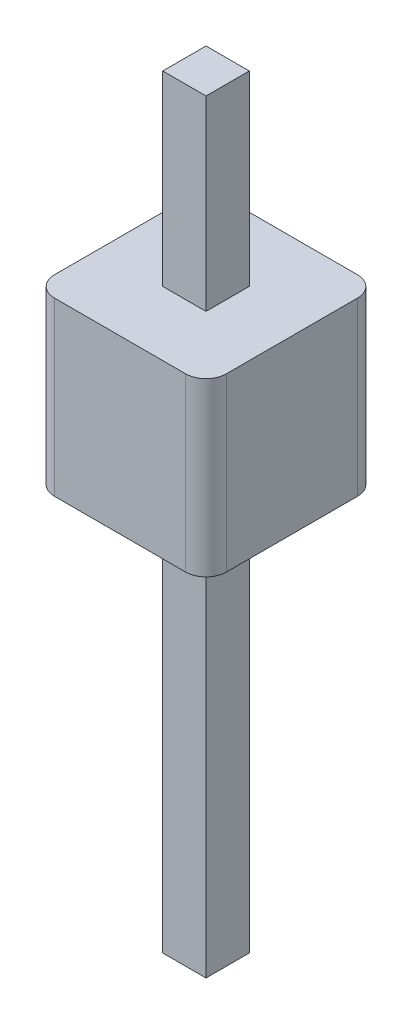
SolidWorks part; units mm, degrees
ref_plane "Front" through (0, 0, 0) normal (0, 0, 1) x (1, 0, 0)
ref_plane "Top" through (0, 0, 0) normal (0, 1, 0) x (1, 0, 0)
ref_plane "Right" through (0, 0, 0) normal (1, 0, 0) x (0, 0, -1)
sketch "Эскиз1" plane through (0, 0, 0) normal (0, 1, 0) x (1, 0, 0)
  line L1 (0.32, -0.32) -> (-0.32, -0.32)
  line L2 (0.32, -0.32) -> (0.32, 0.32)
  line L3 (0.32, 0.32) -> (-0.32, 0.32)
  line L4 (-0.32, -0.32) -> (-0.32, 0.32)
  line L5 (0.32, -0.32) -> (-0.32, 0.32) construction
  line L6 (0.32, 0.32) -> (-0.32, -0.32) construction
  line L7 (0.97, -1.27) -> (-0.97, -1.27)
  line L8 (1.27, -0.97) -> (1.27, 0.97)
  line L9 (0.97, 1.27) -> (-0.97, 1.27)
  line L10 (-1.27, -0.97) -> (-1.27, 0.97)
  line L11 (1.27, -1.27) -> (-1.27, 1.27) construction
  line L12 (1.27, 1.27) -> (-1.27, -1.27) construction
  arc A0 (-0.97, -1.27) -> (-1.27, -0.97) centre (-0.97, -0.97) cw
  arc A1 (0.97, -1.27) -> (1.27, -0.97) centre (0.97, -0.97) ccw
  arc A2 (1.27, 0.97) -> (0.97, 1.27) centre (0.97, 0.97) ccw
  arc A3 (-0.97, 1.27) -> (-1.27, 0.97) centre (-0.97, 0.97) ccw
  point P0 (0, 0)
  point P6 (0, 0)
  dimension "D3" = 0.3
  dimension "D1" = 0.64
  dimension "D2" = 2.54
extrude "Бобышка-Вытянуть1" add sketch "Эскиз1" along normal blind 2.54
extrude "Бобышка-Вытянуть2" add sketch "Эскиз1<2>" along normal blind 5.3 and the other way blind 6 contours L1 L4 L3 L2
sketch "Эскиз1<2>" plane through (0, 0, 0) normal (0, 1, 0) x (1, 0, 0) same geometry as "Эскиз1"
